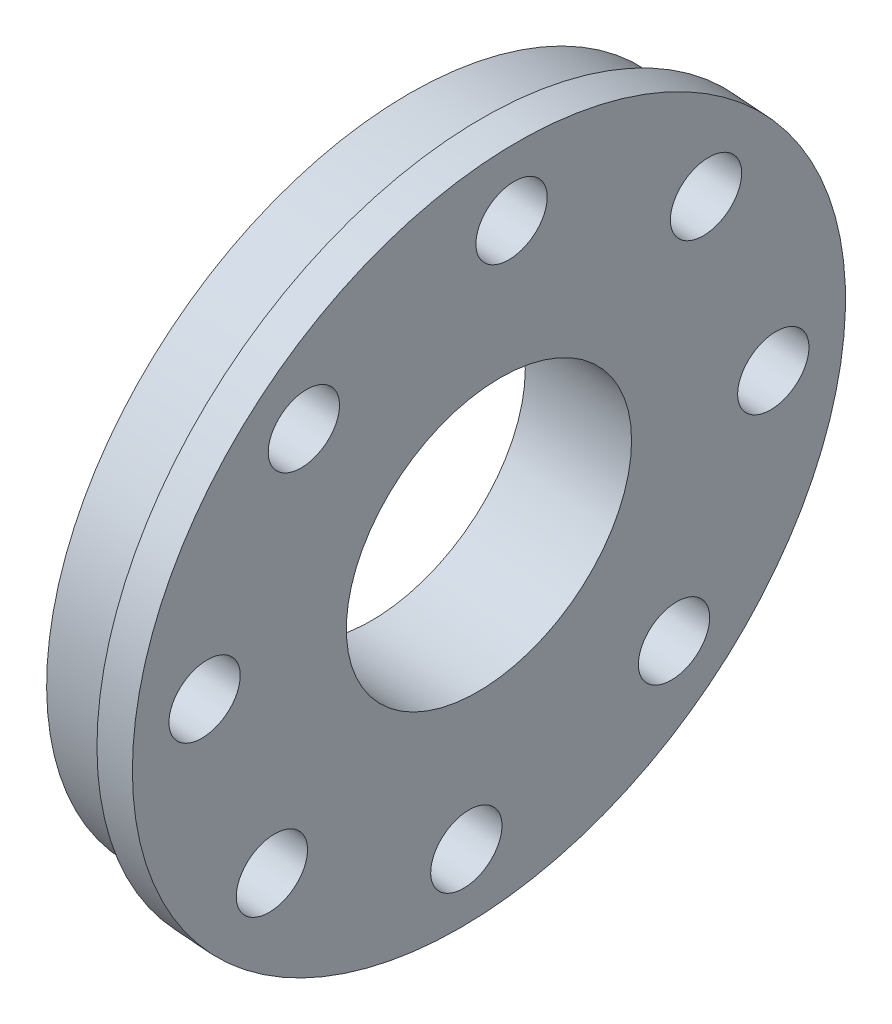
SolidWorks part; units mm, degrees
ref_plane "Front Plane" through (0, 0, 0) normal (0, 0, 1) x (1, 0, 0)
ref_plane "Top Plane" through (0, 0, 0) normal (0, 1, 0) x (1, 0, 0)
ref_plane "Right Plane" through (0, 0, 0) normal (1, 0, 0) x (0, 0, -1)
sketch "Sketch1" plane through (234.2789, -18.689, 0) normal (0.9968, -0.0795, 0) x (0, 0, -1)
  circle A1 centre (-43.1743, 8.5503) radius 14.9606
  dimension "D1" = 29.9212
extrude "Boss-Extrude1" add sketch "Sketch1" against normal blind 4.7625
sketch "Sketch2" plane through (234.2789, -18.689, 0) normal (0.9968, -0.0795, 0) x (0, 0, -1)
  circle A0 centre (-43.1743, 8.5503) radius 6.35
  dimension "D1" = 12.7
extrude "Cut-Extrude1" cut sketch "Sketch2" against normal blind 6.35
sketch "Sketch3" plane through (229.5315, -18.3103, 0) normal (-0.9968, 0.0795, 0) x (0, 0, 1)
  circle A0 centre (43.1743, 21.2503) radius 1.5875
  circle A1 centre (43.1743, 8.5503) radius 14.9606 construction
  circle A2 centre (43.1743, 8.5503) radius 14.9606
  circle A3 centre (52.1545, 17.5306) radius 1.5875
  circle A4 centre (55.8743, 8.5503) radius 1.5875
  circle A5 centre (52.1545, -0.4299) radius 1.5875
  circle A6 centre (43.1743, -4.1497) radius 1.5875
  circle A7 centre (34.194, -0.4299) radius 1.5875
  circle A8 centre (30.4743, 8.5503) radius 1.5875
  circle A9 centre (34.194, 17.5306) radius 1.5875
  point P21 (43.1743, 8.5503)
  dimension "D1" = 3.175
  dimension "D3" = 12.7
  dimension "D2" = 8
extrude "Cut-Extrude2" cut sketch "Sketch3" against normal blind 10 contours A8 | A0 | A3 | A4 | A5 | A6 | A7 | A9 region at (231.2213, 2.8727, 43.1743) region at (230.9255, -0.8352, 52.1545) region at (230.2114, -9.787, 55.8743) region at (229.4973, -18.7389, 52.1545) region at (229.2015, -22.4468, 43.1743) region at (229.4973, -18.7389, 34.194) region at (230.2114, -9.787, 30.4743)
sketch "Sketch4" plane through (234.2789, -18.689, 0) normal (0.9968, -0.0795, 0) x (0, 0, -1)
  line L0 (-58.1349, 8.5503) -> (-28.2137, 8.5503) construction
  circle A0 centre (-43.1743, 8.5503) radius 14.9606 construction
sketch "Sketch5" plane through (234.2789, -18.689, 0) normal (-0.9968, 0.0795, 0) x (0, 0, 1)
  circle A0 centre (43.1743, 8.5503) radius 14.9606 construction
  circle A1 centre (43.1743, 8.5503) radius 14.9606
  circle A2 centre (43.1743, 8.5503) radius 15.875
  dimension "D1" = 31.75
extrude "Boss-Extrude2" add sketch "Sketch5" along normal blind 1.5875
ref_axis "Axis1" through (230.2414, -9.7894, 43.1743) along (0.9968, -0.0795, 0)
ref_point "Point1"
